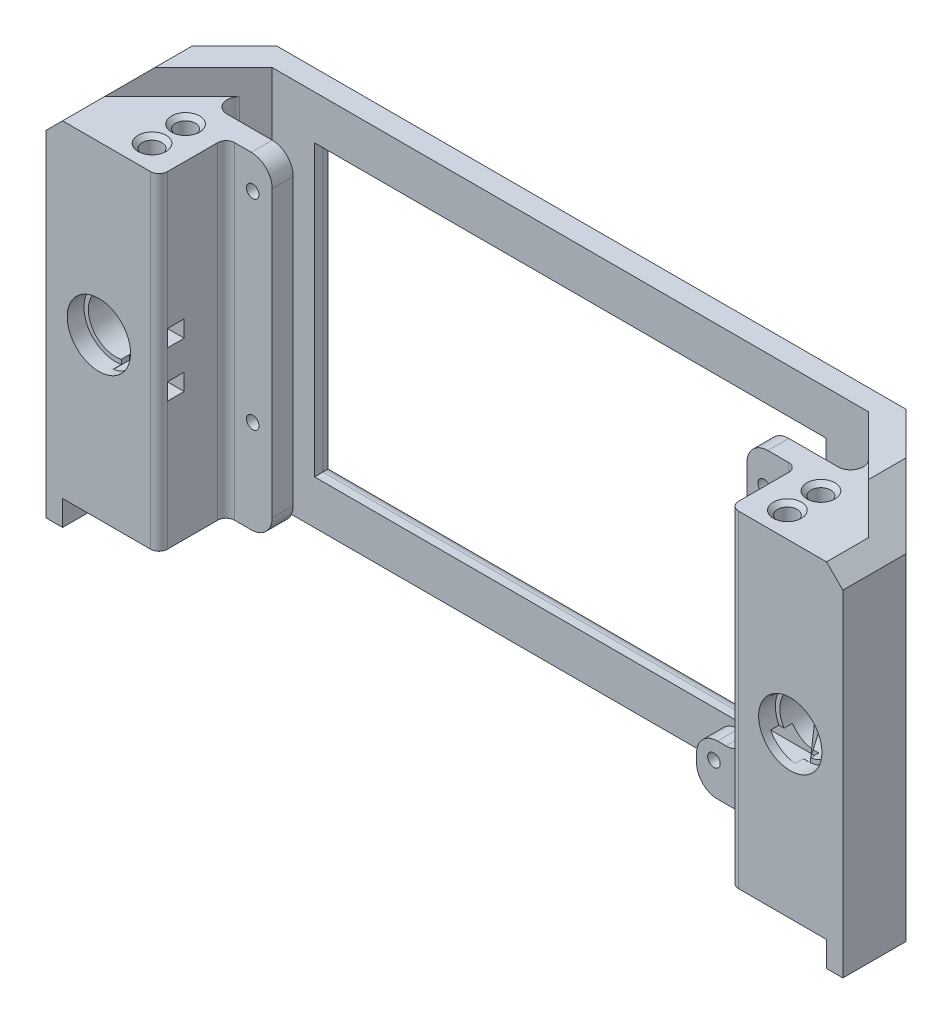
SolidWorks part; units mm, degrees
ref_plane "Front Plane" through (0, 0, 0) normal (0, 0, 1) x (1, 0, 0)
ref_plane "Top Plane" through (0, 0, 0) normal (0, 1, 0) x (1, 0, 0)
ref_plane "Right Plane" through (0, 0, 0) normal (1, 0, 0) x (0, 0, -1)
sketch "Sketch1" plane through (0, 0, 0) normal (0, 0, 1) x (1, 0, 0)
  line L1 (-95, 45) -> (95, 45)
  line L2 (-95, 45) -> (-95, -45)
  line L3 (-95, -45) -> (95, -45)
  line L4 (95, 45) -> (95, -45)
  line L5 (-95, 45) -> (95, -45) construction
  line L6 (-95, -45) -> (95, 45) construction
  line L7 (-61, 34.5) -> (61, 34.5)
  line L8 (-61, 34.5) -> (-61, -34.5)
  line L9 (-61, -34.5) -> (61, -34.5)
  line L10 (61, 34.5) -> (61, -34.5)
  line L11 (-61, 34.5) -> (61, -34.5) construction
  line L12 (-61, -34.5) -> (61, 34.5) construction
  point P0 (0, 0)
  point P6 (0, 0)
  dimension "D1" = 122
  dimension "D2" = 190
  dimension "D3" = 69
  dimension "D4" = 90
extrude "Boss-Extrude1" add sketch "Sketch1" along normal blind 5
sketch "Sketch2" plane through (0, 0, 5) normal (0, 0, 1) x (1, 0, 0)
  line L0 (-95, -45) -> (95, -45) construction
  line L1 (-95, 45) -> (-91.1, 45)
  line L2 (-95, 45) -> (-95, -45)
  line L3 (-95, -45) -> (-91.1, -45)
  line L4 (-91.1, 45) -> (-91.1, -45)
  line L5 (0, 0) -> (0, 45) construction
  line L6 (95, 45) -> (-95, 45) construction
  line L7 (95, -45) -> (91.1, -45)
  line L8 (91.1, 45) -> (91.1, -45)
  line L9 (95, 45) -> (91.1, 45)
  line L10 (95, 45) -> (95, -45)
  dimension "D1" = 3.9
extrude "Boss-Extrude2" add sketch "Sketch2" along normal blind 30
sketch "Sketch3" plane through (0, 45, 0) normal (0, 1, 0) x (1, 0, 0)
  line L0 (-91.1, -35) -> (-91.1, -5) construction
  line L1 (-91.1, -14) -> (-57.1, -14)
  line L2 (-91.1, -14) -> (-91.1, -19)
  line L3 (-91.1, -19) -> (-57.1, -19)
  line L4 (-57.1, -14) -> (-57.1, -19)
  line L5 (91.1, -35) -> (91.1, -5) construction
  line L6 (91.1, -14) -> (44.1, -14)
  line L7 (91.1, -14) -> (91.1, -19)
  line L8 (91.1, -19) -> (44.1, -19)
  line L9 (44.1, -14) -> (44.1, -19)
  line L10 (91.1, -5) -> (-91.1, -5) construction
  dimension "D1" = 9
  dimension "D2" = 9
  dimension "D3" = 5
  dimension "D4" = 5
  dimension "D5" = 34
  dimension "D6" = 47
extrude "Boss-Extrude3" add sketch "Sketch3" against normal up to surface (90 mm away) up to face at (0, -45, 18.75)
sketch "Sketch4" plane through (0, 0, 19) normal (0, 0, 1) x (1, 0, 0)
  line L0 (91.1, -45) -> (91.1, 45) construction
  line L1 (-91.1, 45) -> (91.1, 45)
  line L2 (-91.1, 45) -> (-91.1, 39)
  line L3 (-91.1, 39) -> (91.1, 39)
  line L4 (91.1, 45) -> (91.1, 39)
  line L5 (0, 0) -> (-91.1, 0) construction
  line L6 (-91.1, -45) -> (-91.1, 45) construction
  line L7 (-91.1, -39) -> (91.1, -39)
  line L8 (91.1, -45) -> (91.1, -39)
  line L9 (-91.1, -45) -> (91.1, -45)
  line L10 (-91.1, -45) -> (-91.1, -39)
  dimension "D1" = 6
extrude "Cut-Extrude1" cut sketch "Sketch4" against normal blind 5
sketch "Sketch5" plane through (0, 0, 19) normal (0, 0, 1) x (1, 0, 0)
  line L0 (0, 0) -> (-61.75, 0) construction
  line L1 (-70.2, 37.38) -> (70.2, 37.38) construction
  line L2 (-70.2, 37.38) -> (-70.2, -37.38) construction
  line L3 (-70.2, -37.38) -> (70.2, -37.38) construction
  line L4 (70.2, 37.38) -> (70.2, -37.38) construction
  line L5 (-70.2, 37.38) -> (70.2, -37.38) construction
  line L6 (-70.2, -37.38) -> (70.2, 37.38) construction
  line L7 (-61.75, 0) -> (-61.75, 31.13) construction
  line L8 (-61.75, 0) -> (-61.75, -16.61) construction
  line L9 (48.25, 0) -> (60.23, 0) construction
  line L10 (60.23, 0) -> (60.23, 31.13) construction
  line L11 (0, 0) -> (48.25, 0) construction
  line L12 (48.25, 0) -> (48.25, -31.38) construction
  circle A0 centre (-61.75, 31.13) radius 1.5
  circle A1 centre (-61.75, -16.61) radius 1.5
  circle A2 centre (60.23, 31.13) radius 1.5
  circle A3 centre (48.25, -31.38) radius 1.5
  point P0 (0, 0)
  dimension "D10" = 3
  dimension "D11" = 3
  dimension "D12" = 3
  dimension "D13" = 3
  dimension "D1" = 140.4
  dimension "D2" = 74.76
  dimension "D3" = 61.75
  dimension "D4" = 31.13
  dimension "D5" = 16.61
  dimension "D6" = 60.23
  dimension "D7" = 31.13
  dimension "D8" = 48.25
  dimension "D9" = 31.38
extrude "Cut-Extrude2" cut sketch "Sketch5" against normal up to surface (5 mm away) up to face at (67.6, 0, 14)
sketch "Sketch6" plane through (0, 0, 19) normal (0, 0, 1) x (1, 0, 0)
  line L1 (44.1, 39) -> (56.1, 39)
  line L2 (44.1, 39) -> (44.1, -27)
  line L3 (44.1, -27) -> (56.1, -27)
  line L4 (56.1, 39) -> (56.1, -27)
  dimension "D1" = 12
  dimension "D2" = 66
extrude "Cut-Extrude3" cut sketch "Sketch6" against normal up to surface (5 mm away) up to face at (46.75, -31.38, 14)
fillet "Fillet3" radius 3 4 edges at (-61, 0, 0) (0, -34.5, 0) (61, 0, 0) (0, 34.5, 0)
chamfer "Chamfer6" distance 20 angle 45 4 edges at (91.1, 0, 5) (95, 0, 0) (-95, 0, 0) (-91.1, 0, 5)
sketch "Sketch7" plane through (0, 39, 0) normal (0, 1, 0) x (1, 0, 0)
  line L0 (-85.1, -19) -> (-91.1, -25)
  line L1 (-91.1, -25) -> (-91.1, -35)
  line L2 (-91.1, -35) -> (-68.1, -35)
  line L3 (-68.1, -35) -> (-68.1, -19)
  line L4 (-85.1, -19) -> (-57.1, -19) construction
  line L5 (-68.1, -19) -> (-85.1, -19)
  line L6 (0, 0) -> (0, -5) construction
  line L7 (71.1, -5) -> (-71.1, -5) construction
  line L8 (68.1, -35) -> (68.1, -19)
  line L9 (91.1, -35) -> (68.1, -35)
  line L10 (91.1, -25) -> (91.1, -35)
  line L11 (85.1, -19) -> (91.1, -25)
  line L12 (68.1, -19) -> (85.1, -19)
  dimension "D1" = 23
extrude "Boss-Extrude4" add sketch "Sketch7" against normal up to surface (78 mm away) up to face at (-69.85, -39, 16.5)
fillet "Fillet4" radius 5 6 edges at (-57.1, -39, 16.5) (-57.1, 39, 16.5) (56.1, 39, 16.5) (44.1, -39, 16.5) (44.1, -27, 16.5) (56.1, -27, 16.5)
fillet "Fillet5" radius 2 4 edges at (-68.1, 0, 35) (68.1, 0, 35) (68.1, 0, 19) (-68.1, 0, 19)
fillet "Fillet6" radius 3 2 edges at (-80.1, 0, 14) (80.1, 0, 14)
sketch "Sketch9" plane through (0, 0, 35) normal (0, 0, 1) x (1, 0, 0)
  line L6 (0, 0) -> (0, -45) construction
  line L7 (-71.1, -45) -> (71.1, -45) construction
  line L8 (-95, 45) -> (-95, -45) construction
  line L9 (-95, 39) -> (-82.45, 39) construction
  line L10 (-95, 39) -> (-95, -0.9074) construction
  line L11 (-95, -0.9074) -> (-82.45, -0.9074) construction
  line L12 (-82.45, 39) -> (-82.45, -0.9074) construction
  line L13 (-91.1, 39) -> (-70.1, 39) construction
  circle A0 centre (-82.45, -0.9074) radius 6.5
  circle A1 centre (82.45, -0.9074) radius 6.5
  dimension "D3" = 13
  dimension "D1" = 39.9074
  dimension "D2" = 12.55
extrude "Cut-Extrude4" cut sketch "Sketch9" against normal blind 10
sketch "Sketch10" plane through (0, 0, 35) normal (0, 0, 1) x (1, 0, 0)
  circle A0 centre (-82.45, -0.9074) radius 7.55
  circle A1 centre (82.45, -0.9074) radius 7.55
  dimension "D1" = 15.1
  dimension "D2" = 15.1
extrude "Cut-Extrude5" cut sketch "Sketch10" against normal blind 4
sketch "Sketch12" plane through (-68.1, 0, 0) normal (1, 0, 0) x (0, 0, -1)
  line L0 (-33, -4.4074) -> (-29, -4.4074)
  line L1 (-33, 39) -> (-23, 39) construction
  line L2 (-33, 39) -> (-33, -0.9074) construction
  line L3 (-33, -0.9074) -> (-23, -0.9074) construction
  line L4 (-23, 39) -> (-23, -0.9074) construction
  line L5 (-33, 6.5926) -> (-23, 6.5926) construction
  line L6 (-33, 6.5926) -> (-33, -8.4074) construction
  line L7 (-33, -8.4074) -> (-23, -8.4074) construction
  line L8 (-23, 6.5926) -> (-23, -8.4074) construction
  line L9 (-33, 6.5926) -> (-23, -8.4074) construction
  line L10 (-33, -8.4074) -> (-23, 6.5926) construction
  line L11 (-33, 6.5926) -> (-29, 6.5926)
  line L12 (-33, 6.5926) -> (-33, 2.5926)
  line L13 (-33, 2.5926) -> (-29, 2.5926)
  line L14 (-29, 6.5926) -> (-29, 2.5926)
  line L15 (-29, -8.4074) -> (-29, -4.4074)
  line L16 (-33, -8.4074) -> (-29, -8.4074)
  line L17 (-33, -8.4074) -> (-33, -4.4074)
  point P5 (-28, -0.9074)
  dimension "D1" = 39.9074
  dimension "D2" = 10
  dimension "D3" = 15
  dimension "D4" = 10
  dimension "D5" = 4
  dimension "D6" = 4
extrude "Cut-Extrude6" cut sketch "Sketch12" against normal blind 13 and the other way blind 151.4
sketch "Sketch15" plane through (0, 39, 0) normal (0, 1, 0) x (1, 0, 0)
  line L0 (68.1, -21) -> (68.1, -33) construction
  line L5 (72.8574, -14) -> (61.1, -14) construction
  line L6 (91.1, -35) -> (68.1, -35) construction
  line L7 (91.1, -35) -> (91.1, -14) construction
  line L8 (91.1, -14) -> (68.1, -14) construction
  line L9 (68.1, -35) -> (68.1, -14) construction
  line L10 (68.1, -14) -> (75.7667, -21) construction
  line L11 (75.7667, -21) -> (83.4333, -28) construction
  line L12 (83.4333, -28) -> (91.1, -35) construction
  line L13 (0, 0) -> (0, -5) construction
  line L14 (71.1, -5) -> (-71.1, -5) construction
  line L15 (75.7667, -21) -> (75.7667, -29) construction
  circle A0 centre (75.7667, -21) radius 2.35
  circle A1 centre (83.4333, -28) radius 2.35 construction
  circle A2 centre (-75.7667, -21) radius 2.35
  circle A3 centre (-83.4333, -28) radius 2.35 construction
  circle A4 centre (75.7667, -29) radius 2.35
  circle A5 centre (-75.7667, -29) radius 2.35
  dimension "D1" = 4.7
  dimension "D2" = 4.7
  dimension "D6" = 4.7
  dimension "D3" = 23
  dimension "D4" = 21
  dimension "D5" = 8
extrude "Cut-Extrude7" cut sketch "Sketch15" against normal blind 8
chamfer "Chamfer7" distance 1 angle 45 4 edges at (-75.7667, 39, 18.65) (75.7667, 39, 23.35) (-75.7667, 39, 26.65) (75.7667, 39, 31.35)
sketch "Sketch17" plane through (0, -39, 0) normal (0, -1, 0) x (1, 0, 0)
  line L0 (0, 0) -> (0, 5) construction
  line L1 (91.1, 35) -> (68.1, 35) construction
  line L2 (91.1, 35) -> (91.1, 19) construction
  line L3 (91.1, 19) -> (68.1, 19) construction
  line L4 (68.1, 35) -> (68.1, 19) construction
  line L5 (-71.1, 5) -> (71.1, 5) construction
  line L6 (68.1, 33) -> (68.1, 21) construction
  line L7 (66.1, 19) -> (49.1, 19) construction
  circle A0 centre (79.6, 27) radius 6.1
  circle A1 centre (-79.6, 27) radius 6.1
  dimension "D2" = 12.2
  dimension "D1" = 11.5
  dimension "D3" = 8
extrude "Cut-Extrude8" cut sketch "Sketch17" against normal blind 3.2
fillet "Fillet7" radius 0.2 2 edges at (-85.7, -39, 27) (85.7, -39, 27)
chamfer "Chamfer8" distance 9.9 angle 45 2 edges at (-95, 45, 27.5) (95, 45, 27.5)
